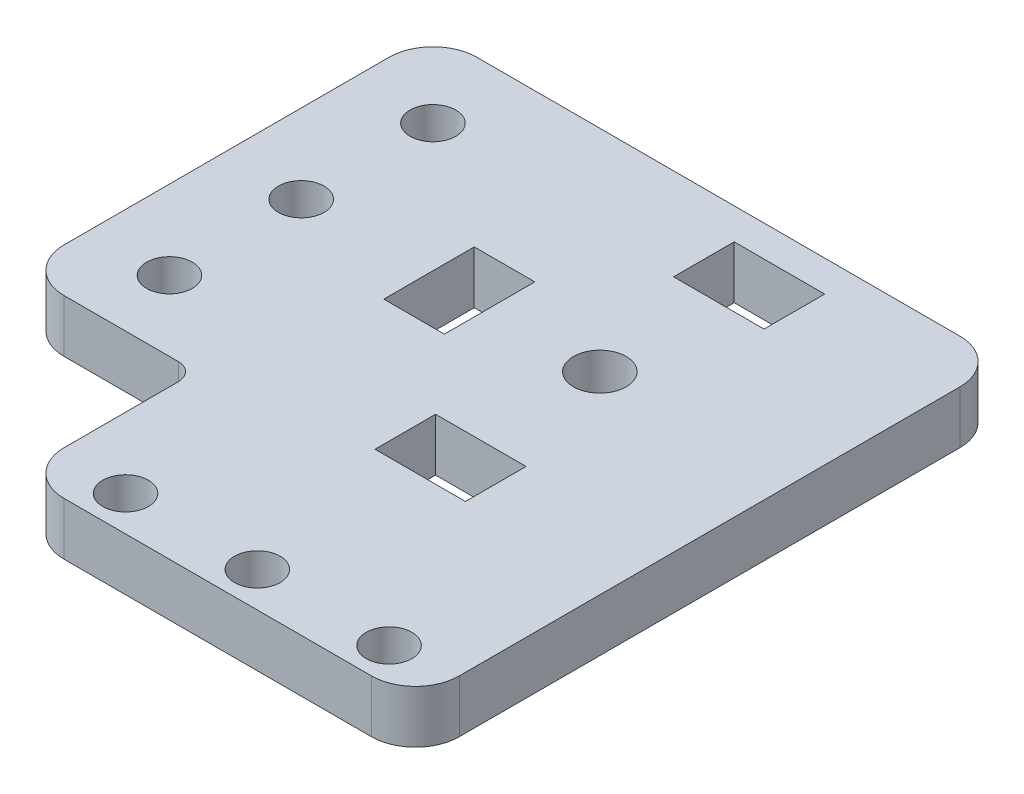
SolidWorks part; units mm, degrees
note: The reader was unsure of these and kept them because the rebuilt part matched: thickness of "Base-Flange1", "Sheet-Metal3", "Sheet-Metal5", "Sheet-Metal6".
material "AISI 4340 Steel, annealed"
ref_plane "Front Plane" through (0, 0, 0) normal (0, 0, 1) x (1, 0, 0)
ref_plane "Top Plane" through (0, 0, 0) normal (0, 1, 0) x (1, 0, 0)
ref_plane "Right Plane" through (0, 0, 0) normal (1, 0, 0) x (0, 0, -1)
sketch "Sketch2" plane through (0, 0, 0) normal (0, 1, 0) x (1, 0, 0)
  line L3 (0, 72) -> (65, 72)
  line L5 (65, 72) -> (65, 5)
  line L6 (65, 5) -> (20, 5)
  line L7 (9, 72) -> (9, 25) construction
  line L11 (20, 72) -> (20, 25) construction
  line L12 (20, 25) -> (65, 25) construction
  line L13 (20, 5) -> (20, 25)
  line L14 (20, 25) -> (0, 25)
  line L16 (0, 25) -> (0, 72)
  line L17 (20, 14) -> (65, 14) construction
  circle A5 centre (28, 9) radius 2.6
  circle A6 centre (43, 9) radius 2.6
  circle A7 centre (58, 9) radius 2.6
  circle A17 centre (9, 33) radius 2.6
  circle A18 centre (9, 48) radius 2.6
  circle A19 centre (9, 63) radius 2.6
  dimension "D9" = 5.2
  dimension "D2" = 15
  dimension "D4" = 8
  dimension "D3" = 15
  dimension "D5" = 20
  dimension "D6" = 15
  dimension "D7" = 15
  dimension "D8" = 8
  dimension "D10" = 9
  dimension "D13" = 9
  dimension "D14" = 65
  dimension "D15" = 67
  dimension "D16" = 20
base flange "Base-Flange1" sketch "Sketch2" thickness 6 reverse thickness direction no parameters "D1"=5
fillet "Fillet1" radius 5 5 edges at (65, -3, -72) (65, -3, -5) (0, -3, -72) (0, -3, -25) (20, -3, -5)
fillet "Fillet2" radius 2 1 edges at (20, -3, -25)
sketch "Sketch5" plane through (0, 0, 0) normal (0, 1, 0) x (1, 0, 0)
  line L1 (5, 25) -> (18, 25) construction
  circle A0 centre (38.8517, 47.1) radius 7.5
  line B0 (19.7517, 52.25) -> (25.9517, 52.25)
  line B1 (19.7517, 41.95) -> (19.7517, 52.25)
  line B2 (25.9517, 41.95) -> (19.7517, 41.95)
  line B3 (25.9517, 52.25) -> (25.9517, 41.95)
  line B4 (57.9517, 41.95) -> (51.7517, 41.95)
  line B5 (51.7517, 52.25) -> (57.9517, 52.25)
  line B6 (57.9517, 52.25) -> (57.9517, 41.95)
  line B7 (51.7517, 41.95) -> (51.7517, 52.25)
  line B8 (44.0017, 27) -> (33.7017, 27)
  line B9 (44.0017, 33.2) -> (44.0017, 27)
  line B10 (33.7017, 33.2) -> (44.0017, 33.2)
  line B11 (33.7017, 27) -> (33.7017, 33.2)
  dimension "D1" = 15
  dimension "D2" = 2
sketch_block_instance "sides Block1-1"
sketch_block "sides Block1" parameters "D1"=14.2405, "D2"=0.5755
extrude "Cut-Extrude2" [suppressed] cut sketch "Sketch5" against normal up to next and the other way through all
sketch "Sketch6" plane through (0, 0, 0) normal (0, 1, 0) x (1, 0, 0)
  line L0 (9, 48) -> (65, 48) construction
  line L1 (65, 10) -> (65, 67) construction
  line L4 (23.55, 42.85) -> (30.45, 42.85)
  line L5 (23.55, 53.15) -> (23.55, 42.85)
  line L6 (30.45, 53.15) -> (23.55, 53.15)
  line L7 (30.45, 42.85) -> (30.45, 53.15)
  line L8 (23.55, 42.85) -> (30.45, 42.85)
  line L9 (23.55, 53.15) -> (23.55, 42.85)
  line L10 (30.45, 53.15) -> (23.55, 53.15)
  line L11 (30.45, 42.85) -> (30.45, 53.15)
  line L12 (37.85, 27.55) -> (48.15, 27.55)
  line L13 (37.85, 34.45) -> (37.85, 27.55)
  line L14 (48.15, 34.45) -> (37.85, 34.45)
  line L15 (48.15, 27.55) -> (48.15, 34.45)
  line L16 (37.85, 27.55) -> (48.15, 27.55)
  line L17 (37.85, 34.45) -> (37.85, 27.55)
  line L18 (48.15, 34.45) -> (37.85, 34.45)
  line L19 (48.15, 27.55) -> (48.15, 34.45)
  line L20 (37.85, 61.55) -> (48.15, 61.55)
  line L21 (37.85, 68.45) -> (37.85, 61.55)
  line L22 (48.15, 68.45) -> (37.85, 68.45)
  line L23 (48.15, 61.55) -> (48.15, 68.45)
  line L24 (37.85, 61.55) -> (48.15, 61.55)
  line L25 (37.85, 68.45) -> (37.85, 61.55)
  line L26 (48.15, 68.45) -> (37.85, 68.45)
  line L27 (48.15, 61.55) -> (48.15, 68.45)
  line L86 (43, 9) -> (43, 72) construction
  line L87 (60, 72) -> (5, 72) construction
  circle A0 centre (43, 48) radius 3
  point P16 (43, 48)
  point P17 (43, 48)
  point P24 (0, 0)
  point P25 (0, 0)
  point P26 (0, 0)
  point P27 (0, 0)
  point P30 (0, 0)
  point P31 (43, 48)
  point P32 (43, 48)
  point P33 (43, 48)
  point P34 (42.9162, 44.517)
  point P35 (0, 0)
  point P36 (0, 0)
  point P38 (0, 0)
  dimension "D4" = 6
  dimension "D1" = 0
  dimension "D2" = 0
  dimension "D3" = 0
extrude "Cut-Extrude3" cut sketch "Sketch6" against normal blind 10 normal cut yes
sketch "Bend-Lines1" [suppressed] plane through (0, 0, 0) normal (0, 1, 0) x (1, 0, 0)
sketch "Bounding-Box1" [suppressed] plane through (0, 0, 0) normal (0, 1, 0) x (1, 0, 0)
sheet metal parameters "Sheet-Metal3" thickness 6 parameters "D1"=5
flat pattern "Flat-Pattern3" [suppressed]
sketch "Bend-Lines2" plane through (0, 0, 0) normal (0, 1, 0) x (1, 0, 0)
sketch3d "Bounding-Box2" [suppressed]
  line L0 (0, 5, 0) -> (65, 5, 0) construction
  line L1 (0, 70, 0) -> (65, 70, 0) construction
  line L2 (0, 5, 0) -> (0, 70, 0) construction
  line L3 (65, 5, 0) -> (65, 70, 0) construction
sheet metal parameters "Sheet-Metal5" thickness 6 parameters "D1"=5, "D7"=3
flat pattern "Flat-Pattern3"
sketch "Bend-Lines2" plane through (0, 0, 0) normal (0, 1, 0) x (1, 0, 0)
sketch3d "Bounding-Box2" [suppressed]
  line L0 (0, 5, 0) -> (65, 5, 0) construction
  line L1 (0, 70, 0) -> (65, 70, 0) construction
  line L2 (0, 5, 0) -> (0, 70, 0) construction
  line L3 (65, 5, 0) -> (65, 70, 0) construction
sheet metal parameters "Sheet-Metal6" thickness 6 parameters "D1"=5
flat pattern "Flat-Pattern3"
sketch "Bend-Lines2" plane through (0, 0, 0) normal (0, 1, 0) x (1, 0, 0)
sketch3d "Bounding-Box2" [suppressed]
  line L0 (65, 72, 0) -> (65, 5, 0) construction
  line L1 (0, 72, 0) -> (0, 5, 0) construction
  line L2 (65, 72, 0) -> (0, 72, 0) construction
  line L3 (65, 5, 0) -> (0, 5, 0) construction
